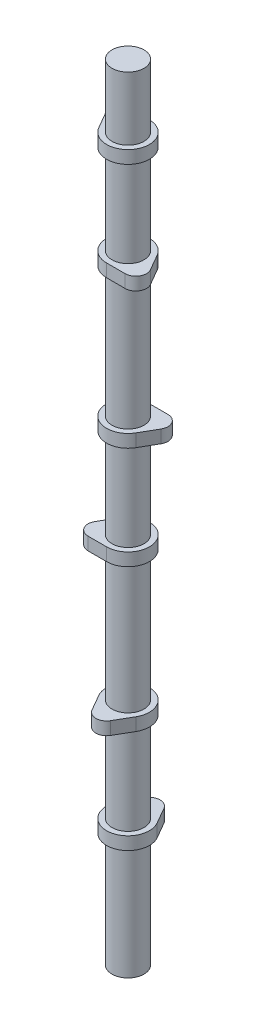
SolidWorks part; units mm, degrees
ref_plane "Front Plane" through (0, 0, 0) normal (0, 0, 1) x (1, 0, 0)
ref_plane "Top Plane" through (0, 0, 0) normal (0, 1, 0) x (1, 0, 0)
ref_plane "Right Plane" through (0, 0, 0) normal (1, 0, 0) x (0, 0, -1)
sketch "Sketch1" plane through (0, 0, 0) normal (0, 1, 0) x (1, 0, 0)
  line L0 (-5.4993, 15.875) -> (-10.9985, 6.35)
  line L1 (5.4993, 15.875) -> (10.9985, 6.35)
  arc A0 (-10.9985, 6.35) -> (10.9985, 6.35) centre (0, 0) ccw
  arc A1 (5.4993, 15.875) -> (-5.4993, 15.875) centre (0, 12.7) ccw
  dimension "D2" = 12.7
  dimension "D3" = 25.4
  dimension "D1" = 12.7
extrude "Boss-Extrude3" add sketch "Sketch1" along normal blind 7.62
ref_axis "Axis1" through (0, 31.1551, 0) along (0, -1, 0)
pattern_linear "LPattern1" count 2 spacing 60.96 along (0, 1, 0) of bodies 103
move or copy body "Body-Move/Copy1" bodies to move or copy 107 copy no rotation origin (0, 0, 0) rotation axis (0, 1, 0) rotation angle 180
pattern_linear "LPattern2" count 3 spacing 146.05 along (0, 1, 0) of bodies 103 108
move or copy body "Body-Move/Copy2" bodies to move or copy 111 109 copy no rotation origin (0, 0, 0) rotation axis (0, 1, 0) rotation angle 120
move or copy body "Body-Move/Copy3" bodies to move or copy 112 110 copy no rotation origin (0, 0, 0) rotation axis (0, -1, 0) rotation angle 120
sketch "Sketch2" plane through (0, 0, 0) normal (0, 1, 0) x (1, 0, 0)
  circle A0 centre (0, 0) radius 9.5
  point P3 (0, 0)
  dimension "D1" = 19
extrude "Boss-Extrude4" add sketch "Sketch2" along normal blind 466.09 from offset 67.8 offset against normal yes
